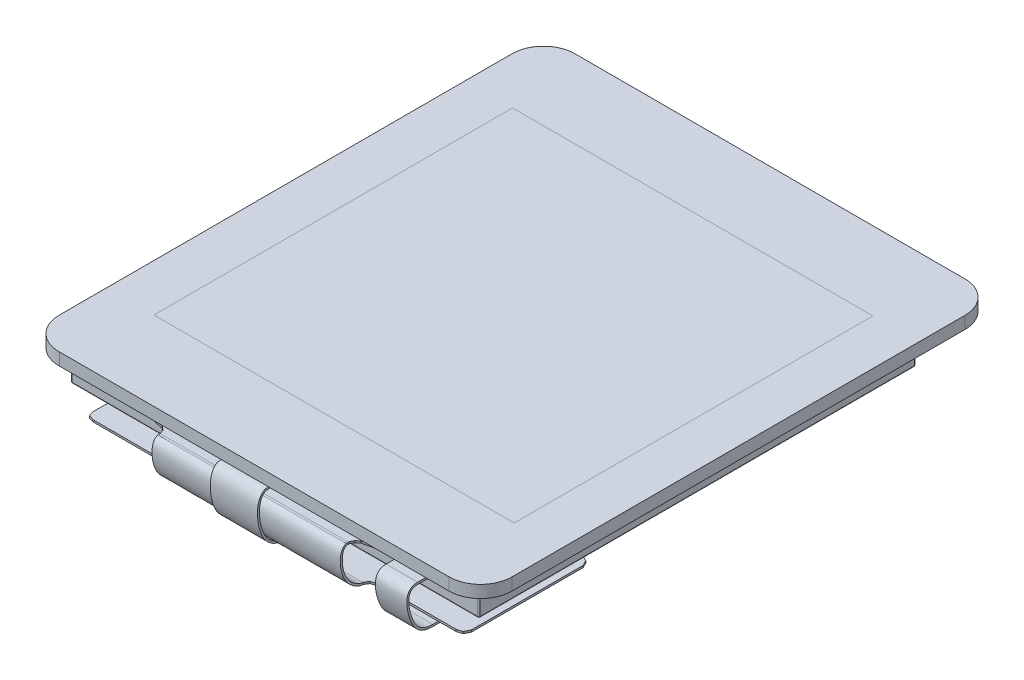
SolidWorks part; units mm, degrees
ref_plane "Ebene vorne" through (0, 0, 0) normal (0, 0, 1) x (1, 0, 0)
ref_plane "Ebene oben" through (0, 0, 0) normal (0, 1, 0) x (1, 0, 0)
ref_plane "Ebene rechts" through (0, 0, 0) normal (1, 0, 0) x (0, 0, -1)
sketch "Skizze1" plane through (0, 0, 0) normal (0, 1, 0) x (1, 0, 0)
  line L0 (-10.3006, -18.7379) -> (-10.4888, -18.361)
  line L1 (10.2585, -18.6958) -> (10.4, -18.361)
  line L4 (-14.0273, -22.8411) -> (-14.0273, -22.7993)
  line L5 (-14.0273, -22.7993) -> (-14.0691, -22.7993)
  line L6 (-14.0691, -22.7993) -> (-14.0691, -22.8411)
  line L7 (-14.0691, -22.8411) -> (-14.0273, -22.8411)
  line L8 (15.7018, -18.361) -> (15.7018, 15.346)
  line L9 (15.7018, 15.346) -> (-15.7858, 15.346)
  line L10 (-15.7858, 15.346) -> (-15.7858, -18.361)
  line L11 (-15.7858, -18.361) -> (15.7018, -18.361)
  line L12 (12.5614, -22.7993) -> (12.5614, -18.361)
  line L13 (10.1331, -22.7993) -> (10.1331, -18.361)
  line L14 (10.1331, -26.3167) -> (10.1331, -18.361)
  line L15 (12.5614, -26.3167) -> (12.5614, -18.361)
  line L16 (10.7611, -26.3167) -> (10.1331, -26.3167)
  line L17 (11.724, -26.3167) -> (10.9705, -26.3167)
  line L18 (11.5986, -26.0233) -> (11.5146, -26.3167)
  line L19 (11.1799, -26.3167) -> (11.0959, -26.0234)
  line L20 (10.9705, -26.3167) -> (10.9705, -26.2327)
  line L21 (10.9705, -26.2327) -> (10.8448, -26.1909)
  line L22 (10.8448, -26.1909) -> (10.7612, -26.2327)
  line L23 (10.7612, -26.2327) -> (10.7612, -26.3167)
  line L24 (10.6354, -26.0233) -> (10.4678, -26.3167)
  line L25 (12.2267, -26.3167) -> (12.1009, -26.0234)
  line L26 (12.0173, -26.3167) -> (11.9334, -26.2327)
  line L27 (11.9334, -26.2327) -> (11.8916, -26.1909)
  line L28 (11.8916, -26.1909) -> (11.724, -26.2327)
  line L29 (11.724, -26.2327) -> (11.724, -26.3167)
  line L30 (12.5614, -26.3167) -> (12.0173, -26.3167)
  line L31 (11.5986, -25.0187) -> (11.5986, -24.0137)
  line L32 (11.5986, -24.0137) -> (12.1009, -24.0137)
  line L33 (12.1009, -24.0137) -> (12.1009, -25.0187)
  line L34 (11.5986, -25.0187) -> (11.5146, -25.2699)
  line L35 (11.5146, -25.2699) -> (11.5986, -25.4792)
  line L36 (11.8915, -25.1441) -> (11.724, -25.1859)
  line L37 (11.724, -25.1859) -> (11.724, -25.3535)
  line L38 (11.724, -25.3535) -> (11.8915, -25.3953)
  line L39 (11.8915, -25.3953) -> (11.9334, -25.3535)
  line L40 (11.9334, -25.3535) -> (12.0173, -25.2699)
  line L41 (12.0173, -25.2699) -> (11.9334, -25.1859)
  line L42 (11.9334, -25.1859) -> (11.8915, -25.1441)
  line L43 (12.1009, -25.4792) -> (12.2267, -25.2699)
  line L44 (12.2267, -25.2699) -> (12.1009, -25.0187)
  line L45 (10.6354, -25.3535) -> (10.6354, -24.0137)
  line L46 (11.0959, -24.0137) -> (11.0959, -25.3535)
  line L47 (11.0959, -25.814) -> (11.0959, -26.0234)
  line L48 (10.6354, -25.814) -> (10.6354, -26.0234)
  line L49 (10.6354, -25.3535) -> (10.4678, -25.5628)
  line L50 (10.4678, -25.5628) -> (10.6354, -25.814)
  line L51 (10.8447, -25.3953) -> (10.7612, -25.4792)
  line L52 (10.7612, -25.4792) -> (10.7612, -25.6046)
  line L53 (10.7612, -25.6046) -> (10.8447, -25.6886)
  line L54 (10.8447, -25.6886) -> (10.9705, -25.6046)
  line L55 (10.9705, -25.6046) -> (10.9705, -25.4792)
  line L56 (10.9705, -25.4792) -> (10.8447, -25.3953)
  line L57 (11.0959, -25.814) -> (11.1799, -25.5628)
  line L58 (11.1799, -25.5628) -> (11.0959, -25.3535)
  line L59 (12.1009, -26.0233) -> (12.1009, -25.4792)
  line L60 (11.5986, -25.4792) -> (11.5986, -26.0233)
  line L61 (10.6354, -24.0137) -> (11.0959, -24.0137)
  line L62 (-13.9015, -13.8387) -> (-13.9015, 13.8387)
  line L63 (-13.9015, 13.8387) -> (13.9015, 13.8387)
  line L64 (13.9015, 13.8387) -> (13.9015, -13.8387)
  line L65 (13.9015, -13.8387) -> (-13.9015, -13.8387)
  line L77 (-7.3278, -19.8683) -> (-7.3278, -22.3806)
  line L78 (-10.1749, -18.8215) -> (-7.7465, -19.366)
  line L80 (-10.3006, -18.7379) -> (-10.1749, -18.8215)
  line L81 (-7.3278, -19.8683) -> (-7.4532, -19.5754)
  line L82 (-7.4532, -19.5754) -> (-7.7465, -19.366)
  line L83 (-7.3278, -19.8683) -> (-7.3278, -22.3806)
  line L84 (-7.7883, -22.8411) -> (-7.4532, -22.7158)
  line L85 (-7.4532, -22.7158) -> (-7.3278, -22.3806)
  line L86 (10.0491, -18.8215) -> (7.6207, -19.366)
  line L87 (10.0491, -18.8215) -> (10.2167, -18.7379)
  line L88 (10.2167, -18.7379) -> (10.2585, -18.6958)
  line L89 (7.6207, -19.366) -> (7.3696, -19.5754)
  line L90 (7.3696, -19.5754) -> (7.202, -19.8683)
  line L91 (7.202, -19.8683) -> (7.202, -22.3806)
  line L92 (3.5171, -58.2648) -> (-3.5593, -58.2648)
  line L93 (3.7265, -52.8214) -> (-3.7686, -52.8214)
  line L94 (3.5171, -58.2648) -> (3.6847, -58.223)
  line L95 (3.6847, -58.223) -> (3.7265, -58.0554)
  line L96 (3.7265, -53.2823) -> (3.7265, -33.8118)
  line L97 (-3.7687, -58.0554) -> (-3.6994, -58.223)
  line L98 (-3.6994, -58.223) -> (-3.5593, -58.2648)
  line L99 (-3.7687, -52.8214) -> (3.7265, -52.8214)
  line L100 (3.7265, -53.2823) -> (3.7265, -58.0554)
  line L101 (3.5171, -58.2648) -> (3.6847, -58.223)
  line L102 (3.6847, -58.223) -> (3.7265, -58.0554)
  line L103 (3.5171, -58.2648) -> (-3.5593, -58.2648)
  line L104 (-3.7687, -58.0554) -> (-3.6994, -58.223)
  line L105 (-3.6994, -58.223) -> (-3.5593, -58.2648)
  line L107 (-3.7687, -58.0554) -> (-3.7687, -33.8118)
  line L108 (-3.7687, -33.8118) -> (-4.1034, -32.9744)
  line L109 (-4.1034, -32.9744) -> (-5.0248, -32.6393)
  line L114 (13.9433, -22.8411) -> (7.7883, -22.8411)
  line L115 (-7.7883, -22.8411) -> (-14.0691, -22.8411)
  line L116 (-14.0691, -22.8411) -> (-14.4878, -22.9669)
  line L117 (-14.4878, -22.9669) -> (-14.6132, -23.3856)
  line L118 (7.202, -22.3806) -> (7.4114, -22.7158)
  line L119 (7.4114, -22.7158) -> (7.7883, -22.8412)
  line L120 (14.5714, -23.3856) -> (14.5714, -32.0112)
  line L121 (14.5714, -23.3856) -> (14.3621, -22.9669)
  line L122 (14.3621, -22.9669) -> (13.9434, -22.8412)
  line L123 (13.9433, -32.6393) -> (4.9409, -32.6393)
  line L124 (4.9409, -32.6393) -> (4.1034, -32.9744)
  line L125 (4.1034, -32.9744) -> (3.7265, -33.8118)
  line L126 (13.9433, -32.6393) -> (14.3621, -32.4299)
  line L127 (14.3621, -32.4299) -> (14.5714, -32.0112)
  line L128 (-5.0248, -32.6393) -> (-14.0691, -32.6393)
  line L129 (-14.6132, -23.3856) -> (-14.6132, -32.0112)
  line L130 (-14.6132, -32.0112) -> (-14.4878, -32.4299)
  line L131 (-14.4878, -32.4299) -> (-14.0691, -32.6393)
  line L132 (-3.0566, -25.3535) -> (-2.7219, -25.1859)
  line L133 (-2.7219, -25.1859) -> (-2.5961, -24.8512)
  line L134 (-2.5961, -24.8511) -> (-2.5961, -19.9519)
  line L135 (1.0466, -24.8511) -> (1.256, -25.1859)
  line L136 (1.256, -25.1859) -> (1.5911, -25.3535)
  line L137 (1.0466, -24.8511) -> (1.0466, -19.9519)
  line L138 (-8.5, -31.2995) -> (-11.3474, -31.2995)
  line L139 (-11.4728, -31.0901) -> (-11.4728, -31.2574)
  line L140 (-11.4728, -31.2574) -> (-11.3474, -31.2995)
  line L141 (-11.4728, -31.0901) -> (-11.4728, -27.9916)
  line L142 (-11.3474, -27.7822) -> (-11.4728, -27.824)
  line L143 (-11.4728, -27.824) -> (-11.4728, -27.9916)
  line L144 (-11.3474, -27.7822) -> (-8.5, -27.7822)
  line L145 (-8.5, -27.7822) -> (-8.5, -31.2995)
  line L146 (-11.4728, -31.0901) -> (-11.4728, -31.2574)
  line L147 (-11.4728, -31.2574) -> (-11.3474, -31.2995)
  line L148 (-11.4728, -31.0901) -> (-11.4728, -27.9916)
  line L149 (-11.3474, -27.7822) -> (-11.4728, -27.824)
  line L150 (-11.4728, -27.824) -> (-11.4728, -27.9916)
  line L151 (-11.3474, -27.7822) -> (-5.0248, -27.7822)
  line L152 (-5.0248, -27.7822) -> (-4.6897, -27.6146)
  line L153 (-4.6897, -27.6146) -> (-4.5221, -27.2795)
  line L154 (-14.0273, -22.8411) -> (-14.0273, -22.7993)
  line L155 (-14.0273, -22.7993) -> (-14.0691, -22.7993)
  line L156 (-14.0691, -22.7993) -> (-14.0691, -22.8411)
  line L157 (-14.0691, -22.8411) -> (-14.0273, -22.8411)
  line L158 (10.6354, -27.3635) -> (10.6354, -23.8044)
  line L159 (10.6354, -23.8044) -> (11.0959, -23.8044)
  line L160 (11.0959, -23.8044) -> (11.0959, -27.3635)
  line L161 (11.0959, -27.3635) -> (10.6354, -27.3635)
  line L162 (11.5986, -27.3635) -> (11.5986, -23.8044)
  line L163 (11.5986, -23.8044) -> (12.1009, -23.8044)
  line L164 (12.1009, -23.8044) -> (12.1009, -27.3635)
  line L165 (12.1009, -27.3635) -> (11.5986, -27.3635)
  line L166 (10.7611, -28.8708) -> (10.7611, -28.0334)
  line L167 (11.1799, -28.4521) -> (10.3424, -28.4521)
  line L168 (11.6822, -28.4521) -> (12.4778, -28.4521)
  line L169 (-7.7883, -24.1813) -> (-7.7883, -23.8044)
  line L170 (-7.7883, -23.8044) -> (-5.9877, -23.8044)
  line L171 (-5.9877, -23.8044) -> (-5.9877, -24.1813)
  line L172 (-5.9877, -24.1813) -> (-7.7883, -24.1813)
  line L173 (-7.7883, -24.8511) -> (-7.7883, -24.516)
  line L174 (-7.7883, -24.516) -> (-5.9877, -24.516)
  line L175 (-5.9877, -24.516) -> (-5.9877, -24.8511)
  line L176 (-5.9877, -24.8511) -> (-7.7883, -24.8511)
  line L177 (-7.7883, -25.4792) -> (-7.7883, -25.1441)
  line L178 (-7.7883, -25.1441) -> (-5.9877, -25.1441)
  line L179 (-5.9877, -25.1441) -> (-5.9877, -25.4792)
  line L180 (-5.9877, -25.4792) -> (-7.7883, -25.4792)
  line L181 (-7.7883, -26.1073) -> (-7.7883, -25.7722)
  line L182 (-7.7883, -25.7722) -> (-5.9877, -25.7722)
  line L183 (-5.9877, -25.7722) -> (-5.9877, -26.1073)
  line L184 (-5.9877, -26.1073) -> (-7.7883, -26.1073)
  line L185 (-11.8079, -24.1813) -> (-11.8079, -23.8044)
  line L186 (-11.8079, -23.8044) -> (-13.6504, -23.8044)
  line L187 (-13.6504, -23.8044) -> (-13.6504, -24.1813)
  line L188 (-13.6504, -24.1813) -> (-11.8079, -24.1813)
  line L189 (-11.8079, -24.8511) -> (-11.8079, -24.516)
  line L190 (-11.8079, -24.516) -> (-13.6504, -24.516)
  line L191 (-13.6504, -24.516) -> (-13.6504, -24.8511)
  line L192 (-13.6504, -24.8511) -> (-11.8079, -24.8511)
  line L193 (-11.8079, -25.4792) -> (-11.8079, -25.1441)
  line L194 (-11.8079, -25.1441) -> (-13.6504, -25.1441)
  line L195 (-13.6504, -25.1441) -> (-13.6504, -25.4792)
  line L196 (-13.6504, -25.4792) -> (-11.8079, -25.4792)
  line L197 (-11.8079, -26.1073) -> (-11.8079, -25.7722)
  line L198 (-11.8079, -25.7722) -> (-13.6504, -25.7722)
  line L199 (-13.6504, -25.7722) -> (-13.6504, -26.1073)
  line L200 (-13.6504, -26.1073) -> (-11.8079, -26.1073)
  line L201 (-11.3474, -31.2995) -> (-5.0248, -31.2995)
  line L202 (-4.5221, -31.8018) -> (-4.6897, -31.4667)
  line L203 (-4.6897, -31.4667) -> (-5.0248, -31.2995)
  line L204 (1.8005, -31.8018) -> (1.9262, -31.8018)
  line L205 (1.9262, -31.8018) -> (2.0098, -31.6343)
  line L206 (2.0098, -31.6343) -> (2.0098, -25.5628)
  line L207 (2.0098, -25.5628) -> (1.9262, -25.3953)
  line L208 (1.9262, -25.3953) -> (1.8005, -25.3535)
  line L209 (1.8005, -25.3535) -> (-4.3128, -25.3535)
  line L210 (-4.3128, -25.3535) -> (-4.4803, -25.3953)
  line L211 (-4.4803, -25.3953) -> (-4.5221, -25.5628)
  line L212 (-4.5221, -25.5628) -> (-4.5221, -31.6343)
  line L213 (-4.5221, -31.6343) -> (-4.4803, -31.8018)
  line L214 (-4.4803, -31.8018) -> (-4.3128, -31.8018)
  line L215 (-4.3128, -31.8018) -> (1.8005, -31.8018)
  line L216 (14.9901, -19.9519) -> (16.2463, -19.6589)
  line L217 (16.2463, -19.6589) -> (17.1674, -18.7379)
  line L218 (17.1674, -18.7379) -> (17.4189, -17.5235)
  line L219 (17.4189, -17.5235) -> (17.4189, 17.4396)
  line L220 (17.4189, 17.4396) -> (17.1674, 18.6957)
  line L221 (17.1674, 18.6957) -> (16.2463, 19.575)
  line L222 (16.2463, 19.575) -> (14.9902, 19.8683)
  line L223 (14.9901, 19.8683) -> (-15.0741, 19.8683)
  line L224 (-15.0741, 19.8683) -> (-16.2881, 19.575)
  line L225 (-16.2881, 19.575) -> (-17.1677, 18.6957)
  line L226 (-17.1677, 18.6957) -> (-17.5442, 17.4396)
  line L227 (-17.5443, 17.4396) -> (-17.5443, -17.5236)
  line L228 (-17.5443, -17.5235) -> (-17.1677, -18.7379)
  line L229 (-17.1677, -18.7379) -> (-16.2881, -19.6589)
  line L230 (-16.2881, -19.6589) -> (-15.0741, -19.9519)
  line L231 (-15.0741, -19.9519) -> (14.9902, -19.9519)
  line L232 (-13.9015, 13.8387) -> (-13.9015, -13.8387)
  line L233 (-13.9015, -13.8387) -> (13.9015, -13.8387)
  line L234 (13.9015, -13.8387) -> (13.9015, 13.8387)
  line L235 (13.9015, 13.8387) -> (-13.9015, 13.8387)
  line L236 (-12.5659, -28.1971) -> (-12.5659, -28.5322)
  line L237 (-12.5659, -28.5322) -> (-13.3197, -28.5322)
  line L238 (-13.3197, -28.5322) -> (-13.3197, -28.1971)
  line L239 (-13.3197, -28.1971) -> (-12.5659, -28.1971)
  line L240 (-12.5659, -28.6998) -> (-12.5659, -29.0349)
  line L241 (-12.5659, -29.0349) -> (-13.3197, -29.0349)
  line L242 (-13.3197, -29.0349) -> (-13.3197, -28.6998)
  line L243 (-13.3197, -28.6998) -> (-12.5659, -28.6998)
  line L244 (-12.5659, -29.2439) -> (-12.5659, -29.4951)
  line L245 (-12.5659, -29.4951) -> (-13.3197, -29.4951)
  line L246 (-13.3197, -29.4951) -> (-13.3197, -29.2439)
  line L247 (-13.3197, -29.2439) -> (-12.5659, -29.2439)
  line L248 (-12.5659, -29.7048) -> (-12.5659, -29.9977)
  line L249 (-12.5659, -29.9977) -> (-13.3197, -29.9977)
  line L250 (-13.3197, -29.9977) -> (-13.3197, -29.7048)
  line L251 (-13.3197, -29.7048) -> (-12.5659, -29.7048)
  line L252 (-12.5659, -30.2071) -> (-12.5659, -30.5001)
  line L253 (-12.5659, -30.5001) -> (-13.3197, -30.5001)
  line L254 (-13.3197, -30.5001) -> (-13.3197, -30.2071)
  line L255 (-13.3197, -30.2071) -> (-12.5659, -30.2071)
  line L256 (-12.5659, -30.7094) -> (-12.5659, -31.0446)
  line L257 (-12.5659, -31.0446) -> (-13.3197, -31.0446)
  line L258 (-13.3197, -31.0446) -> (-13.3197, -30.7094)
  line L259 (-13.3197, -30.7094) -> (-12.5659, -30.7094)
  point P1 (0, 0)
sketch "Skizze3" plane through (0, 0, 0) normal (0, 1, 0) x (1, 0, 0)
  line L0 (15.7018, -18.361) -> (15.7018, 15.346)
  line L1 (-15.7858, 15.346) -> (15.7018, 15.346)
  line L2 (-15.7858, 15.346) -> (-15.7858, -18.361)
  line L3 (-15.7858, -18.361) -> (15.7018, -18.361)
  point P0 (0, 0)
extrude "Aufsatz-Linear austragen1" add sketch "Skizze3" along normal blind 2.275
sketch "Skizze2" plane through (0, 0, 0) normal (0, 1, 0) x (1, 0, 0)
  line L3 (17.4189, -17.5232) -> (17.4189, 17.4396)
  line L7 (14.9901, 19.8683) -> (-15.0741, 19.8683)
  line L11 (-17.5443, 17.4396) -> (-17.5443, -17.5236)
  line L15 (-15.0741, -19.9519) -> (14.9902, -19.9519)
  arc A0 (-17.5443, 17.4396) -> (-15.0741, 19.8683) centre (-15.1152, 17.4396) cw
  arc A1 (14.9901, 19.8683) -> (17.4189, 17.4396) centre (14.9901, 17.4396) cw
  arc A2 (-17.5443, -17.5236) -> (-15.0741, -19.9519) centre (-15.1156, -17.5236) ccw
  arc A3 (14.9902, -19.9519) -> (17.4189, -17.5232) centre (14.9902, -17.5232) ccw
  point P0 (0, 0)
extrude "Aufsatz-Linear austragen2" add sketch "Skizze2" along normal offset from surface (0.95 mm away) 3.225 from surface separate body up to face at (-0.042, 0, 1.5075) starting at face at (-0.042, 2.275, 1.5075)
sketch "Skizze4" plane through (0, 3.225, 0) normal (0, 1, 0) x (1, 0, 0)
  line L0 (-13.9015, -13.8387) -> (-13.9015, 13.8387)
  line L1 (-13.9015, 13.8387) -> (13.9015, 13.8387)
  line L2 (13.9015, 13.8387) -> (13.9015, -13.8387)
  line L3 (13.9015, -13.8387) -> (-13.9015, -13.8387)
  point P0 (0, 0)
split line "Trennlinie1"
sketch "Skizze5" plane through (0, 0, 0) normal (0, 1, 0) x (1, 0, 0)
  line L0 (-10.3006, -18.7379) -> (-10.4888, -18.361)
  line L1 (-7.3278, -19.9519) -> (7.202, -19.9519)
  line L7 (-7.3278, -19.8683) -> (-7.4532, -19.5754)
  line L9 (10.0491, -18.8215) -> (7.6207, -19.366)
  line L10 (7.202, -19.9519) -> (7.202, -19.8683)
  line L11 (-15.0741, -19.9519) -> (14.9902, -19.9519) construction
  line L12 (7.3696, -19.5754) -> (7.6207, -19.366)
  line L13 (7.3696, -19.5754) -> (7.202, -19.8683)
  line L14 (10.0491, -18.8215) -> (10.1331, -18.7796)
  line L15 (-10.3006, -18.7379) -> (-10.1749, -18.8215)
  line L16 (-7.7465, -19.366) -> (-7.4532, -19.5754)
  line L17 (-10.4888, -18.361) -> (12.5614, -18.361)
  line L18 (10.1331, -19.9519) -> (12.5614, -19.9519)
  line L19 (-7.3278, -19.8683) -> (-7.3278, -19.9519)
  line L20 (10.1331, -18.7796) -> (10.1331, -19.9519)
  line L21 (12.5614, -18.361) -> (12.5614, -19.9519)
  line L22 (-10.1749, -18.8215) -> (-7.7465, -19.366)
  point P1 (0, 0)
extrude "Aufsatz-Linear austragen3" add sketch "Skizze5" along normal blind 0.15 from offset 1.5 separate body contours L15 L22 L16 L7 L19 L1 L10 L13 L12 L9 L14 L20 L18 L21 L17 L0 region at (1.315, 0, 19.1017)
sketch "Skizze6" plane through (0, 0, 0) normal (0, 1, 0) x (1, 0, 0)
  line L2 (-2.5961, -19.9519) -> (-2.5961, -18.361)
  line L3 (-15.7858, -18.361) -> (15.7018, -18.361) construction
  line L4 (-2.5961, -19.9519) -> (1.0466, -19.9519)
  line L5 (-2.5961, -18.361) -> (1.0466, -18.361)
  line L6 (-10.4888, -18.361) -> (12.5614, -18.361) construction
  line L7 (1.0466, -18.361) -> (1.0466, -19.9519)
  point P0 (0, 0)
extrude "Aufsatz-Linear austragen4" add sketch "Skizze6" against normal blind 0.15 from surface separate body starting at face at (-0.042, 2.275, 1.5075)
sketch "Skizze7" plane through (0, 0, 0) normal (0, 1, 0) x (1, 0, 0)
  line L194 (-13.3197, -10.4927) -> (-12.5659, -10.4927)
  line L195 (-13.3197, -10.1576) -> (-13.3197, -10.4927)
  line L196 (-12.5659, -10.1576) -> (-13.3197, -10.1576)
  line L197 (-12.5659, -10.4927) -> (-12.5659, -10.1576)
  line L198 (-13.3197, -10.995) -> (-12.5659, -10.995)
  line L199 (-13.3197, -10.7021) -> (-13.3197, -10.995)
  line L200 (-12.5659, -10.7021) -> (-13.3197, -10.7021)
  line L201 (-12.5659, -10.995) -> (-12.5659, -10.7021)
  line L202 (-13.3197, -11.4974) -> (-12.5659, -11.4974)
  line L203 (-13.3197, -11.2044) -> (-13.3197, -11.4974)
  line L204 (-12.5659, -11.2044) -> (-13.3197, -11.2044)
  line L205 (-12.5659, -11.4974) -> (-12.5659, -11.2044)
  line L206 (-13.3197, -11.9582) -> (-12.5659, -11.9582)
  line L207 (-13.3197, -11.7071) -> (-13.3197, -11.9582)
  line L208 (-12.5659, -11.7071) -> (-13.3197, -11.7071)
  line L209 (-12.5659, -11.9582) -> (-12.5659, -11.7071)
  line L210 (-13.3197, -12.5023) -> (-12.5659, -12.5023)
  line L211 (-13.3197, -12.1672) -> (-13.3197, -12.5023)
  line L212 (-12.5659, -12.1672) -> (-13.3197, -12.1672)
  line L213 (-12.5659, -12.5023) -> (-12.5659, -12.1672)
  line L214 (-13.3197, -13.005) -> (-12.5659, -13.005)
  line L215 (-13.3197, -12.6699) -> (-13.3197, -13.005)
  line L216 (-12.5659, -12.6699) -> (-13.3197, -12.6699)
  line L217 (-12.5659, -13.005) -> (-12.5659, -12.6699)
  line L218 (-9.5538, -5.8259) -> (-3.4405, -5.8259)
  line L219 (-9.7213, -5.8259) -> (-9.5537, -5.8259)
  line L220 (-9.7631, -5.9934) -> (-9.7213, -5.8259)
  line L221 (-9.7631, -12.0649) -> (-9.7631, -5.9934)
  line L222 (-9.7213, -12.2324) -> (-9.7631, -12.0649)
  line L223 (-9.5538, -12.2742) -> (-9.7213, -12.2324)
  line L224 (-3.4405, -12.2742) -> (-9.5537, -12.2742)
  line L225 (-3.3147, -12.2324) -> (-3.4405, -12.2742)
  line L226 (-3.2311, -12.0649) -> (-3.3147, -12.2324)
  line L227 (-3.2311, -5.9934) -> (-3.2311, -12.0649)
  line L228 (-3.3147, -5.8259) -> (-3.2311, -5.9934)
  line L229 (-3.4405, -5.8259) -> (-3.3147, -5.8259)
  line L230 (-9.9307, -6.161) -> (-10.2658, -6.3282)
  line L231 (-9.7631, -5.8259) -> (-9.9307, -6.161)
  line L232 (-11.3474, -9.9026) -> (-5.0248, -9.9026)
  line L233 (-13.6504, -15.0948) -> (-11.8079, -15.0948)
  line L234 (-13.6504, -15.43) -> (-13.6504, -15.0948)
  line L235 (-11.8079, -15.43) -> (-13.6504, -15.43)
  line L236 (-11.8079, -15.0948) -> (-11.8079, -15.43)
  line L237 (-13.6504, -15.7229) -> (-11.8079, -15.7229)
  line L238 (-13.6504, -16.058) -> (-13.6504, -15.7229)
  line L239 (-11.8079, -16.058) -> (-13.6504, -16.058)
  line L240 (-11.8079, -15.7229) -> (-11.8079, -16.058)
  line L241 (-13.6504, -16.351) -> (-11.8079, -16.351)
  line L242 (-13.6504, -16.6861) -> (-13.6504, -16.351)
  line L243 (-11.8079, -16.6861) -> (-13.6504, -16.6861)
  line L244 (-11.8079, -16.351) -> (-11.8079, -16.6861)
  line L245 (-13.6504, -17.0209) -> (-11.8079, -17.0209)
  line L246 (-13.6504, -17.3978) -> (-13.6504, -17.0209)
  line L247 (-11.8079, -17.3978) -> (-13.6504, -17.3978)
  line L248 (-11.8079, -17.0209) -> (-11.8079, -17.3978)
  line L249 (-5.9877, -15.0948) -> (-7.7883, -15.0948)
  line L250 (-5.9877, -15.43) -> (-5.9877, -15.0948)
  line L251 (-7.7883, -15.43) -> (-5.9877, -15.43)
  line L252 (-7.7883, -15.0948) -> (-7.7883, -15.43)
  line L253 (-5.9877, -15.7229) -> (-7.7883, -15.7229)
  line L254 (-5.9877, -16.058) -> (-5.9877, -15.7229)
  line L255 (-7.7883, -16.058) -> (-5.9877, -16.058)
  line L256 (-7.7883, -15.7229) -> (-7.7883, -16.058)
  line L257 (-5.9877, -16.351) -> (-7.7883, -16.351)
  line L258 (-5.9877, -16.6861) -> (-5.9877, -16.351)
  line L259 (-7.7883, -16.6861) -> (-5.9877, -16.6861)
  line L260 (-7.7883, -16.351) -> (-7.7883, -16.6861)
  line L261 (-5.9877, -17.0209) -> (-7.7883, -17.0209)
  line L262 (-5.9877, -17.3978) -> (-5.9877, -17.0209)
  line L263 (-7.7883, -17.3978) -> (-5.9877, -17.3978)
  line L264 (-7.7883, -17.0209) -> (-7.7883, -17.3978)
  line L265 (11.6822, -12.7501) -> (12.4778, -12.7501)
  line L266 (11.1799, -12.7501) -> (10.3424, -12.7501)
  line L267 (10.7611, -12.3313) -> (10.7611, -13.1688)
  line L268 (12.1009, -13.8387) -> (11.5986, -13.8387)
  line L269 (12.1009, -17.3978) -> (12.1009, -13.8387)
  line L270 (11.5986, -17.3978) -> (12.1009, -17.3978)
  line L271 (11.5986, -13.8387) -> (11.5986, -17.3978)
  line L272 (11.0959, -13.8387) -> (10.6354, -13.8387)
  line L273 (11.0959, -17.3978) -> (11.0959, -13.8387)
  line L274 (10.6354, -17.3978) -> (11.0959, -17.3978)
  line L275 (10.6354, -13.8387) -> (10.6354, -17.3978)
  line L280 (-9.9306, -10.0131) -> (-9.7631, -10.3482)
  line L281 (-10.2658, -9.8455) -> (-9.9306, -10.0131)
  line L282 (-22.0679, -9.8455) -> (-10.2658, -9.8455)
  line L283 (-11.4728, -13.3782) -> (-11.4728, -13.2106)
  line L284 (-22.0679, -9.8455) -> (-11.4728, -13.3782)
  line L285 (-11.4728, -10.112) -> (-11.4728, -13.2106)
  line L286 (-11.4728, -9.9448) -> (-11.3474, -9.9026)
  line L287 (-11.4728, -10.112) -> (-11.4728, -9.9448)
  line L288 (-8.5, -13.42) -> (-8.5, -9.9026)
  line L289 (-22.0679, -9.8455) -> (-8.5, -13.42)
  line L290 (-11.4728, -13.3782) -> (-11.4728, -13.2106)
  line L291 (-22.0679, -9.8455) -> (-11.4728, -13.3782)
  line L292 (-11.4728, -10.112) -> (-11.4728, -13.2106)
  line L293 (-11.4728, -9.9448) -> (-11.3474, -9.9026)
  line L294 (-11.4728, -10.112) -> (-11.4728, -9.9448)
  line L295 (-8.5, -9.9026) -> (-11.3474, -9.9026)
  line L296 (-3.985, -12.4418) -> (-3.6499, -12.2742)
  line L297 (-4.1944, -12.7766) -> (-3.985, -12.4418)
  line L298 (-7.9628, -12.4418) -> (-7.8371, -12.7766)
  line L299 (-8.2976, -12.2742) -> (-7.9628, -12.4418)
  line L300 (-14.4878, -8.7722) -> (-14.0691, -8.5629)
  line L301 (-14.6132, -9.191) -> (-14.4878, -8.7722)
  line L302 (-14.6132, -17.8165) -> (-14.6132, -9.1909)
  line L303 (-5.0248, -8.5629) -> (-14.0691, -8.5629)
  line L304 (14.3621, -8.7722) -> (14.5714, -9.191)
  line L305 (13.9433, -8.5629) -> (14.3621, -8.7722)
  line L306 (4.1034, -8.2277) -> (3.7265, -7.3903)
  line L307 (4.9409, -8.5629) -> (4.1034, -8.2277)
  line L308 (13.9433, -8.5629) -> (4.9409, -8.5629)
  line L309 (14.3621, -18.2352) -> (13.9434, -18.361)
  line L310 (14.5714, -17.8165) -> (14.3621, -18.2352)
  line L311 (14.5714, -17.8165) -> (14.5714, -9.1909)
  line L312 (7.4114, -18.4864) -> (7.7883, -18.361)
  line L313 (7.202, -18.8215) -> (7.4114, -18.4864)
  line L314 (-14.4878, -18.2352) -> (-14.6132, -17.8165)
  line L315 (-14.0691, -18.361) -> (-14.4878, -18.2352)
  line L316 (-7.7883, -18.361) -> (-14.0691, -18.361)
  line L317 (13.9433, -18.361) -> (7.7883, -18.361)
  line L318 (-4.1034, -8.2277) -> (-5.0248, -8.5629)
  line L319 (-3.7687, -7.3903) -> (-4.1034, -8.2277)
  line L320 (-3.7687, 16.8533) -> (-3.7687, -7.3903)
  line L321 (-3.6994, 17.0208) -> (-3.5593, 17.0627)
  line L322 (-3.7687, 16.8533) -> (-3.6994, 17.0208)
  line L323 (3.5171, 17.0626) -> (-3.5593, 17.0626)
  line L324 (3.6847, 17.0208) -> (3.7265, 16.8533)
  line L325 (3.5171, 17.0626) -> (3.6847, 17.0208)
  line L326 (3.7265, 12.0802) -> (3.7265, 16.8533)
  line L327 (-3.7687, 11.6193) -> (3.7265, 11.6193)
  line L328 (-3.6994, 17.0208) -> (-3.5593, 17.0627)
  line L329 (-3.7687, 16.8533) -> (-3.6994, 17.0208)
  line L330 (3.7265, 12.0802) -> (3.7265, -7.3903)
  line L331 (3.6847, 17.0208) -> (3.7265, 16.8533)
  line L332 (3.5171, 17.0626) -> (3.6847, 17.0208)
  line L333 (3.7265, 11.6193) -> (-3.7686, 11.6193)
  line L334 (3.5171, 17.0626) -> (-3.5593, 17.0626)
  line L335 (-7.4532, -18.4864) -> (-7.3278, -18.8215)
  line L336 (-7.7883, -18.361) -> (-7.4532, -18.4864)
  line L337 (10.6354, -17.1884) -> (11.0959, -17.1884)
  line L338 (11.5986, -15.7229) -> (11.5986, -15.1788)
  line L339 (12.1009, -15.1788) -> (12.1009, -15.7229)
  line L340 (11.1799, -15.6393) -> (11.0959, -15.8487)
  line L341 (11.0959, -15.3882) -> (11.1799, -15.6393)
  line L342 (10.9705, -15.7229) -> (10.8447, -15.8069)
  line L343 (10.9705, -15.5975) -> (10.9705, -15.7229)
  line L344 (10.8447, -15.5136) -> (10.9705, -15.5975)
  line L345 (10.7612, -15.5975) -> (10.8447, -15.5136)
  line L346 (10.7612, -15.7229) -> (10.7612, -15.5975)
  line L347 (10.8447, -15.8069) -> (10.7612, -15.7229)
  line L348 (10.4678, -15.6393) -> (10.6354, -15.3881)
  line L349 (10.6354, -15.8487) -> (10.4678, -15.6393)
  line L350 (10.6354, -15.3882) -> (10.6354, -15.1788)
  line L351 (11.0959, -15.3882) -> (11.0959, -15.1788)
  line L352 (11.0959, -17.1884) -> (11.0959, -15.8487)
  line L353 (10.6354, -15.8487) -> (10.6354, -17.1884)
  line L354 (12.2267, -15.9323) -> (12.1009, -16.1834)
  line L355 (12.1009, -15.7229) -> (12.2267, -15.9323)
  line L356 (11.9334, -16.0162) -> (11.8915, -16.058)
  line L357 (12.0173, -15.9323) -> (11.9334, -16.0162)
  line L358 (11.9334, -15.8487) -> (12.0173, -15.9323)
  line L359 (11.8915, -15.8069) -> (11.9334, -15.8487)
  line L360 (11.724, -15.8487) -> (11.8915, -15.8069)
  line L361 (11.724, -16.0162) -> (11.724, -15.8487)
  line L362 (11.8915, -16.058) -> (11.724, -16.0162)
  line L363 (11.5146, -15.9323) -> (11.5986, -15.7229)
  line L364 (11.5986, -16.1834) -> (11.5146, -15.9323)
  line L365 (12.1009, -17.1884) -> (12.1009, -16.1834)
  line L366 (11.5986, -17.1884) -> (12.1009, -17.1884)
  line L367 (11.5986, -16.1834) -> (11.5986, -17.1884)
  line L368 (12.5614, -14.8855) -> (12.0173, -14.8855)
  line L369 (11.724, -14.9694) -> (11.724, -14.8855)
  line L370 (11.8916, -15.0112) -> (11.724, -14.9694)
  line L371 (11.9334, -14.9694) -> (11.8916, -15.0112)
  line L372 (12.0173, -14.8855) -> (11.9334, -14.9694)
  line L373 (12.2267, -14.8855) -> (12.1009, -15.1788)
  line L374 (10.6354, -15.1788) -> (10.4678, -14.8855)
  line L375 (10.7612, -14.9694) -> (10.7612, -14.8855)
  line L376 (10.8448, -15.0112) -> (10.7612, -14.9694)
  line L377 (10.9705, -14.9694) -> (10.8448, -15.0112)
  line L378 (10.9705, -14.8855) -> (10.9705, -14.9694)
  line L379 (11.1799, -14.8855) -> (11.0959, -15.1788)
  line L380 (11.5986, -15.1788) -> (11.5146, -14.8855)
  line L381 (11.724, -14.8855) -> (10.9705, -14.8855)
  line L382 (10.7611, -14.8855) -> (10.1331, -14.8855)
  point P0 (-5.241, -9.9504)
  point P1 (0, 0)
sketch "Skizze8" plane through (0, 0, 0) normal (0, 1, 0) x (1, 0, 0)
  line L24 (-7.3278, -18.8215) -> (7.202, -18.8215)
  line L25 (7.7883, -18.361) -> (13.9433, -18.361)
  line L26 (-3.7687, -7.3903) -> (-4.1034, -8.2277)
  line L27 (3.7265, -7.3903) -> (4.1034, -8.2277)
  line L28 (4.9409, -8.5629) -> (13.9433, -8.5629)
  line L29 (14.3621, -8.7722) -> (14.5714, -9.1909)
  line L30 (14.5714, -17.8165) -> (14.3621, -18.2352)
  line L31 (7.7883, -18.361) -> (7.4114, -18.4864)
  line L32 (-5.0248, -8.5629) -> (-14.0691, -8.5629)
  line L33 (-14.4878, -8.7722) -> (-14.6132, -9.1909)
  line L34 (-14.6132, -17.8165) -> (-14.4878, -18.2352)
  line L35 (-14.0691, -18.361) -> (-7.7883, -18.361)
  line L36 (-7.4532, -18.4864) -> (-7.3278, -18.8215)
  line L37 (4.1034, -8.2277) -> (4.9409, -8.5629)
  line L38 (13.9433, -8.5629) -> (14.3621, -8.7722)
  line L71 (14.5714, -9.1909) -> (14.5714, -17.8165)
  line L72 (14.3621, -18.2352) -> (13.9433, -18.361)
  line L73 (7.4114, -18.4864) -> (7.202, -18.8215)
  line L82 (-7.4532, -18.4864) -> (-7.7883, -18.361)
  line L83 (-14.0691, -18.361) -> (-14.4878, -18.2352)
  line L84 (-14.6132, -17.8165) -> (-14.6132, -9.1909)
  line L85 (-5.0248, -8.5629) -> (-4.1034, -8.2277)
  line L86 (-14.4878, -8.7722) -> (-14.0691, -8.5629)
  line L87 (-3.7687, -7.3903) -> (-3.7687, 16.8533)
  line L89 (3.7265, -7.3903) -> (3.7265, 16.8533)
  line L90 (-3.5593, 17.0627) -> (3.5171, 17.0627)
  line L91 (-3.7687, 16.8533) -> (-3.6994, 17.0208)
  line L92 (3.7265, 16.8533) -> (3.6847, 17.0209)
  line L93 (-3.6994, 17.0208) -> (-3.5593, 17.0627)
  line L94 (3.5171, 17.0627) -> (3.6847, 17.0209)
  line L96 (-3.7687, 8.4252) -> (3.7265, 8.4252)
  line L119 (13.9433, -18.361) -> (7.7883, -18.361)
  point P1 (0, 0)
extrude "Aufsatz-Linear austragen5" add sketch "Skizze8" against normal blind 0.15 from offset 1.6 separate body contours L94 L90 L93 L91 L87 L26 L85 L32 L86 L33 L84 L34 L83 L35 L82 L36 L24 L73 L31 L25 L72 L30 L71 L29 L38 L28 L37 L27 L89 L92 region at (-0.0231, 0, 9.4807) offset against normal yes
sketch "Skizze9" plane through (0, 0, 0) normal (0, 1, 0) x (1, 0, 0)
  line L0 (-2.5961, -18.7299) -> (1.0466, -18.7299)
  line L1 (-3.0566, -15.8487) -> (-4.3128, -15.8487)
  line L2 (-5.0248, -13.42) -> (-4.6897, -13.5875)
  line L3 (-4.5221, -13.9226) -> (-4.5221, -15.6393)
  line L4 (-4.4803, -15.8069) -> (-4.3128, -15.8487)
  line L5 (-3.0566, -15.8487) -> (-2.7219, -16.0162)
  line L6 (1.0466, -16.351) -> (1.256, -16.0162)
  line L7 (1.5911, -15.8487) -> (1.8005, -15.8487)
  line L9 (1.9262, -15.8069) -> (2.0098, -15.6393)
  line L10 (-11.3474, -9.9026) -> (-11.4728, -9.9448)
  line L11 (-11.3474, -13.42) -> (-11.4728, -13.3782)
  line L12 (-4.6897, -13.5875) -> (-4.5221, -13.9226)
  line L13 (-4.5221, -15.6393) -> (-4.4803, -15.8069)
  line L14 (-2.7219, -16.0162) -> (-2.5961, -16.351)
  line L16 (-5.0248, -9.9026) -> (-4.6897, -9.7354)
  line L17 (1.256, -16.0162) -> (1.5911, -15.8487)
  line L18 (2.0098, -15.6393) -> (2.0098, -9.5679)
  line L19 (-4.6897, -9.7354) -> (-4.5221, -9.4003)
  line L20 (-5.0248, -9.9026) -> (-11.3474, -9.9026)
  line L21 (-5.9362, -9.9026) -> (-5.9362, -13.42)
  line L38 (-4.5221, -9.4003) -> (1.9262, -9.4003)
  line L45 (1.9262, -15.8069) -> (1.8005, -15.8487)
  line L48 (1.9262, -9.4003) -> (2.0098, -9.5679)
  line L58 (-11.4728, -9.9448) -> (-11.4728, -13.3782)
  line L62 (-11.3474, -13.42) -> (-5.0248, -13.42)
  line L65 (-11.4728, -9.9448) -> (-11.4728, -13.3782)
  line L69 (1.0466, -16.351) -> (1.0466, -18.7299)
  line L72 (-2.5961, -16.351) -> (-2.5961, -18.7299)
  point P4 (0, 0)
extrude "Aufsatz-Linear austragen6" add sketch "Skizze9" against normal blind 0.15 from surface separate body contours L14 L72 L0 L69 L6 L17 L7 L45 L9 L18 L48 L38 L19 L16 L20 L10 L58 L11 L62 L2 L12 L3 L13 L4 L1 L5 region at (-1.5183, 0, 13.3935) starting at face at (-0.0355, -1.75, 11.7203)
sketch "Skizze10" plane through (0, 0, 0) normal (1, 0, 0) x (0, 0, -1)
  line L0 (-19.9519, 1.5) -> (-19.9519, 1.65)
  line L1 (-18.8215, -1.6) -> (-18.8215, -1.75)
  line L4 (-20.1019, 1.6299) -> (-20.1019, 1.65) construction
  line L5 (-18.9715, -1.7346) -> (-18.9715, -1.75) construction
  arc A0 (-20.1019, 1.6299) -> (-19.9519, 1.65) centre (-19.9567, 1.1166) cw
  arc A1 (-18.8215, -1.75) -> (-18.9715, -1.7346) centre (-18.8215, -1.0126) cw
  spline S0 degree 3 poles (-19.9519, 1.5) (-20.5381, 1.5) (-20.4456, 0.116) (-19.8473, -1.1972) (-19.1556, -1.6) (-18.8215, -1.6) knots 0 0 0 0 0.401622 0.501622 1 1 1 1
  spline S1 degree 1 poles (-20.1019, 1.6299) (-18.9715, -1.7346) knots 0 0 1 1 construction
  spline S2 degree 3 poles (-20.1019, 1.6299) (-20.1984, 1.6026) (-20.3769, 1.4788) (-20.5455, 1.1191) (-20.5815, 0.5548) (-20.4618, -0.1651) (-20.2543, -0.6952) (-19.971, -1.0991) (-19.6408, -1.4173) (-19.2913, -1.6365) (-19.0848, -1.7125) (-18.9715, -1.7346) knots 0.026925 0.026925 0.026925 0.026925 0.084237 0.14155 0.256175 0.3708 0.485424 0.600049 0.714674 0.829299 0.943924 0.943924 0.943924 0.943924
  dimension "D1" = 0.15
extrude "Aufsatz-Linear austragen7" add sketch "Skizze10" along normal up to vertex (7.202 mm away) and the other way up to vertex (7.3278 mm away) up to point (7.202, 1.5, 19.9519) other way up to point (-7.3278, -1.75, 18.8215)
sketch "Skizze11" plane through (0, 0, 0) normal (1, 0, 0) x (0, 0, -1)
  line L0 (-18.7299, -1.9) -> (-18.7299, -1.75)
  line L1 (-19.9519, 2.275) -> (-19.9519, 2.125)
  spline S0 degree 3 poles (-19.9519, 2.275) (-20.7319, 2.275) (-20.9442, 0.9749) (-20.3068, -1.5688) (-19.3098, -1.9) (-18.7299, -1.9) knots 0 0 0 0 0.380799 0.480799 1 1 1 1
  spline S1 degree 1 poles (-19.9519, 2.125) (-18.7299, -1.75) knots 0 0 1 1 construction
  spline S2 degree 3 poles (-19.9519, 2.125) (-20.0429, 2.125) (-20.2356, 2.0811) (-20.4795, 1.8553) (-20.7534, 1.041) (-20.4523, -0.7497) (-19.7491, -1.4807) (-19.1373, -1.7206) (-18.87, -1.75) (-18.7299, -1.75) knots 0 0 0 0 0.0625 0.125 0.25 0.5 0.75 0.875 1 1 1 1
  dimension "D1" = 0.15
extrude "Aufsatz-Linear austragen8" add sketch "Skizze11" against normal up to vertex (2.5961 mm away) and the other way up to vertex (1.0466 mm away) up to point (-2.5961, 2.275, 19.9519) other way up to point (1.0466, 2.275, 19.9519)
sketch "Skizze12" plane through (0, 0, 0) normal (0, 1, 0) x (1, 0, 0)
  line L0 (10.6354, -14.8855) -> (10.6354, -15.4029)
  line L1 (10.6354, -17.1884) -> (11.0959, -17.1884)
  line L2 (11.0959, -17.1884) -> (11.0959, -15.8757)
  line L3 (11.5986, -14.8855) -> (11.5986, -15.7247)
  line L10 (11.5986, -17.1884) -> (12.1009, -17.1884)
  line L11 (12.1009, -17.1884) -> (12.1009, -16.1527)
  line L12 (10.1331, -14.8855) -> (10.7557, -14.8855)
  line L13 (10.9757, -14.8855) -> (11.7397, -14.8855)
  line L14 (11.9597, -14.8855) -> (12.5614, -14.8855)
  line L15 (11.5986, -16.1527) -> (11.5986, -17.1884)
  line L24 (12.1009, -15.7247) -> (12.1009, -14.8855)
  line L25 (10.6354, -15.8757) -> (10.6354, -17.1884)
  line L26 (11.0959, -15.4029) -> (11.0959, -14.8855)
  line L40 (10.1331, -18.7796) -> (10.1331, -14.8855)
  line L41 (12.5614, -14.8855) -> (12.5614, -18.7796)
  line L42 (12.5614, -18.361) -> (12.5614, -19.9519) construction
  line L43 (12.5614, -18.7796) -> (10.1331, -18.7796)
  circle A0 centre (10.8657, -15.6393) radius 0.15
  circle A1 centre (11.8497, -15.9387) radius 0.15
  arc A2 (11.0959, -15.8757) -> (11.0959, -15.4029) centre (10.8657, -15.6393) ccw
  arc A3 (11.5986, -15.7247) -> (11.5986, -16.1527) centre (11.8497, -15.9387) ccw
  arc A4 (10.7557, -14.8855) -> (10.9757, -14.8855) centre (10.8657, -14.8855) ccw
  arc A5 (11.7397, -14.8855) -> (11.9597, -14.8855) centre (11.8497, -14.8855) ccw
  arc A6 (10.6354, -15.4029) -> (10.6354, -15.8757) centre (10.8657, -15.6393) ccw
  arc A7 (12.1009, -16.1527) -> (12.1009, -15.7247) centre (11.8497, -15.9387) ccw
  point P0 (0, 0)
extrude "Aufsatz-Linear austragen9" add sketch "Skizze12" against normal blind 0.15 from surface separate body contours A7 L11 L10 L15 A3 L3 L13 L26 A2 L2 L1 L25 A6 L0 L12 L40 L43 L41 L14 L24 | L11 A7 L24 L14 A5 L13 L3 A3 L15 L10 A1 | L0 A6 L25 L1 L2 A2 L26 L13 A4 L12 A0 region at (10.8657, 0, 16.0594) region at (11.3385, 0, 17.0967) region at (11.6692, 0, 14.9094) starting at face at (-0.134, -1.75, 12.661)
sketch "Skizze13" plane through (0, 0, 0) normal (1, 0, 0) x (0, 0, -1)
  line L0 (-19.9519, 1.65) -> (-19.9519, 1.5)
  line L2 (-18.7796, -1.9) -> (-18.7796, -1.75)
  spline S0 degree 3 poles (-19.9519, 1.65) (-21.0132, 1.65) (-20.7532, -0.6413) (-19.8315, -1.9) (-18.7796, -1.9) knots 0 0 0 0 0.524833 1 1 1 1
  spline S1 degree 3 poles (-19.9519, 2.275) (-20.7319, 2.275) (-20.9442, 0.9749) (-20.3068, -1.5688) (-19.3098, -1.9) (-18.7299, -1.9) knots 0 0 0 0 0.380799 0.480799 1 1 1 1 construction
  spline S2 degree 1 poles (-19.9519, 1.5) (-18.7796, -1.75) knots 0 0 1 1 construction
  spline S3 degree 3 poles (-19.9519, 1.5) (-20.0469, 1.5) (-20.2589, 1.4692) (-20.4279, 1.3625) (-20.5514, 1.2012) (-20.6483, 0.8978) (-20.6413, 0.3828) (-20.4703, -0.3059) (-20.2312, -0.9183) (-19.9137, -1.3771) (-19.5419, -1.6228) (-19.1541, -1.7304) (-18.8998, -1.75) (-18.7796, -1.75) knots 0 0 0 0 0.0625 0.125 0.1875 0.25 0.375 0.5 0.625 0.75 0.875 0.9375 1 1 1 1
  dimension "D1" = 0.15
extrude "Aufsatz-Linear austragen11" add sketch "Skizze13" along normal up to vertex (12.5614 mm away) from vertex up to point (12.5614, 1.65, 19.9519) starting at point (10.1331, 1.65, 19.9519)
sketch "Skizze14" plane through (0, -1.75, 0) normal (0, 1, 0) x (1, 0, 0)
  line L0 (-13.2862, -10.5672) -> (-12.5324, -10.5672)
  line L1 (-13.2862, -10.2321) -> (-13.2862, -10.5672)
  line L2 (-12.5324, -10.2321) -> (-13.2862, -10.2321)
  line L3 (-12.5324, -10.5672) -> (-12.5324, -10.2321)
  line L4 (-13.2862, -11.0695) -> (-12.5324, -11.0695)
  line L5 (-13.2862, -10.7474) -> (-13.2862, -11.0695)
  line L6 (-12.5324, -10.7474) -> (-13.2862, -10.7474)
  line L7 (-12.5324, -11.0695) -> (-12.5324, -10.7474)
  line L8 (-13.2862, -11.5718) -> (-12.5324, -11.5718)
  line L9 (-13.2862, -11.2545) -> (-13.2862, -11.5718)
  line L10 (-12.5324, -11.2545) -> (-13.2862, -11.2545)
  line L11 (-12.5324, -11.5718) -> (-12.5324, -11.2545)
  line L12 (-13.2862, -12.0843) -> (-12.5324, -12.0843)
  line L13 (-13.2862, -11.7532) -> (-13.2862, -12.0843)
  line L14 (-12.5324, -11.7532) -> (-13.2862, -11.7532)
  line L15 (-12.5324, -12.0843) -> (-12.5324, -11.7532)
  line L16 (-13.2862, -12.5768) -> (-12.5324, -12.5768)
  line L17 (-13.2862, -12.2417) -> (-13.2862, -12.5768)
  line L18 (-12.5324, -12.2417) -> (-13.2862, -12.2417)
  line L19 (-12.5324, -12.5768) -> (-12.5324, -12.2417)
  line L20 (-13.2862, -13.0795) -> (-12.5324, -13.0795)
  line L21 (-13.2862, -12.7444) -> (-13.2862, -13.0795)
  line L22 (-12.5324, -12.7444) -> (-13.2862, -12.7444)
  line L23 (-12.5324, -13.0795) -> (-12.5324, -12.7444)
  line L24 (-13.6504, -15.0948) -> (-11.8079, -15.0948)
  line L25 (-13.6504, -15.43) -> (-13.6504, -15.0948)
  line L26 (-11.8079, -15.43) -> (-13.6504, -15.43)
  line L27 (-11.8079, -15.0948) -> (-11.8079, -15.43)
  line L28 (-13.6504, -15.7229) -> (-11.8079, -15.7229)
  line L29 (-13.6504, -16.058) -> (-13.6504, -15.7229)
  line L30 (-11.8079, -16.058) -> (-13.6504, -16.058)
  line L31 (-11.8079, -15.7229) -> (-11.8079, -16.058)
  line L32 (-13.6504, -16.351) -> (-11.8079, -16.351)
  line L33 (-13.6504, -16.6861) -> (-13.6504, -16.351)
  line L34 (-11.8079, -16.6861) -> (-13.6504, -16.6861)
  line L35 (-11.8079, -16.351) -> (-11.8079, -16.6861)
  line L36 (-13.6504, -17.0209) -> (-11.8079, -17.0209)
  line L37 (-13.6504, -17.3978) -> (-13.6504, -17.0209)
  line L38 (-11.8079, -17.3978) -> (-13.6504, -17.3978)
  line L39 (-11.8079, -17.0209) -> (-11.8079, -17.3978)
  line L40 (-5.9877, -15.0948) -> (-7.7883, -15.0948)
  line L41 (-5.9877, -15.43) -> (-5.9877, -15.0948)
  line L42 (-7.7883, -15.43) -> (-5.9877, -15.43)
  line L43 (-7.7883, -15.0948) -> (-7.7883, -15.43)
  line L44 (-5.9877, -15.7229) -> (-7.7883, -15.7229)
  line L45 (-5.9877, -16.058) -> (-5.9877, -15.7229)
  line L46 (-7.7883, -16.058) -> (-5.9877, -16.058)
  line L47 (-7.7883, -15.7229) -> (-7.7883, -16.058)
  line L48 (-5.9877, -16.351) -> (-7.7883, -16.351)
  line L49 (-5.9877, -16.6861) -> (-5.9877, -16.351)
  line L50 (-7.7883, -16.6861) -> (-5.9877, -16.6861)
  line L51 (-7.7883, -16.351) -> (-7.7883, -16.6861)
  line L52 (-5.9877, -17.0209) -> (-7.7883, -17.0209)
  line L53 (-5.9877, -17.3978) -> (-5.9877, -17.0209)
  line L54 (-7.7883, -17.3978) -> (-5.9877, -17.3978)
  line L55 (-7.7883, -17.0209) -> (-7.7883, -17.3978)
  line L56 (12.1009, -13.8387) -> (11.5986, -13.8387)
  line L57 (12.1009, -17.3978) -> (12.1009, -13.8387)
  line L58 (11.5986, -17.3978) -> (12.1009, -17.3978)
  line L59 (11.5986, -13.8387) -> (11.5986, -17.3978)
  line L60 (11.0959, -13.8387) -> (10.6354, -13.8387)
  line L61 (11.0959, -17.3978) -> (11.0959, -13.8387)
  line L62 (10.6354, -17.3978) -> (11.0959, -17.3978)
  line L63 (10.6354, -13.8387) -> (10.6354, -17.3978)
  line L64 (11.0959, -17.1884) -> (11.0959, -15.8487)
  line L65 (10.6354, -15.8487) -> (10.6354, -17.1884)
  line L66 (12.1009, -17.1884) -> (12.1009, -16.1834)
  line L67 (11.5986, -16.1834) -> (11.5986, -17.1884)
  point P0 (0, 0)
split line "Trennlinie2"
sketch "Skizze16" plane through (0, -1.9, 0) normal (0, -1, 0) x (1, 0, 0)
  line L0 (10.7557, 14.8855) -> (10.6354, 14.8855)
  line L1 (11.9597, 14.8855) -> (12.1009, 14.8855)
  line L2 (11.5986, 14.8855) -> (11.7397, 14.8855)
  line L12 (11.0959, 15.4029) -> (11.0959, 14.8855)
  line L13 (10.6354, 15.8757) -> (10.6354, 17.1884)
  line L14 (12.1009, 15.7247) -> (12.1009, 14.8855)
  line L15 (11.5986, 16.1527) -> (11.5986, 17.1884)
  line L16 (10.9757, 14.8855) -> (11.0959, 14.8855)
  line L17 (12.1009, 17.1884) -> (12.1009, 16.1527)
  line L18 (11.5986, 17.1884) -> (12.1009, 17.1884)
  line L19 (11.5986, 14.8855) -> (11.5986, 15.7247)
  line L20 (11.0959, 17.1884) -> (11.0959, 15.8757)
  line L21 (10.6354, 17.1884) -> (11.0959, 17.1884)
  line L22 (10.6354, 14.8855) -> (10.6354, 15.4029)
  arc A8 (12.1009, 16.1527) -> (12.1009, 15.7247) centre (11.8497, 15.9387) cw
  arc A9 (10.6354, 15.4029) -> (10.6354, 15.8757) centre (10.8657, 15.6393) cw
  arc A10 (11.7397, 14.8855) -> (11.9597, 14.8855) centre (11.8497, 14.8855) cw
  arc A11 (10.7557, 14.8855) -> (10.9757, 14.8855) centre (10.8657, 14.8855) cw
  arc A12 (11.5986, 15.7247) -> (11.5986, 16.1527) centre (11.8497, 15.9387) cw
  arc A13 (11.0959, 15.8757) -> (11.0959, 15.4029) centre (10.8657, 15.6393) cw
  circle A14 centre (11.8497, 15.9387) radius 0.15
  circle A15 centre (10.8657, 15.6393) radius 0.15
  point P73 (0, 0)
split line "Trennlinie3"
sketch "Skizze17" plane through (0, 0, 14.8855) normal (0, 0, -1) x (-1, 0, 0)
  line L0 (-10.6354, -1.9) -> (-10.6354, -1.75)
  line L1 (-10.6354, -1.75) -> (-11.0959, -1.75)
  line L2 (-11.0959, -1.75) -> (-11.0959, -1.9)
  line L3 (-11.0959, -1.9) -> (-10.6354, -1.9)
  line L4 (-11.5986, -1.9) -> (-11.5986, -1.75)
  line L5 (-11.5986, -1.75) -> (-12.1009, -1.75)
  line L6 (-12.1009, -1.75) -> (-12.1009, -1.9)
  line L7 (-12.1009, -1.9) -> (-11.5986, -1.9)
split line "Trennlinie4"
fillet "Verrundung1" radius 0.1 8 edges at (-15.7858, 1.1375, 18.361) (-15.7858, 0, 1.5075) (-15.7858, 1.1375, -15.346) (-0.042, 0, -15.346) (15.7018, 1.1375, -15.346) (-0.042, 0, 18.361) (15.7018, 0, 1.5075) (15.7018, 1.1375, 18.361)
sketch "Skizze19" plane through (0, 0, 0) normal (0, 1, 0) x (1, 0, 0)
  line L0 (-3.5593, 17.0627) -> (3.5171, 17.0627)
  line L1 (-3.7687, 16.8533) -> (-3.6994, 17.0208)
  line L2 (3.7265, 16.8533) -> (3.6847, 17.0209)
  line L3 (-3.6994, 17.0208) -> (-3.5593, 17.0627)
  line L4 (3.5171, 17.0627) -> (3.6847, 17.0209)
  line L5 (-3.7687, 11.899) -> (3.7265, 11.899)
  line L6 (-3.7687, 16.8533) -> (-3.7687, 11.899)
  line L7 (3.7265, 16.8533) -> (3.7265, 11.899)
  point P1 (0, 0)
extrude "Aufsatz-Linear austragen12" add sketch "Skizze19" against normal blind 0.15 from offset 2.3 separate body offset against normal yes
sketch "Skizze20" plane through (-3.7687, 0, 0) normal (-1, 0, 0) x (0, 0, 1)
  line L0 (-11.899, -2.45) -> (-11.899, -2.3) construction
  line L1 (-8.4252, -1.75) -> (-8.4252, -1.6) construction
  line L2 (-11.899, -2.3) -> (-11.899, -2.45)
  line L3 (-8.4252, -1.6) -> (-8.4252, -1.75)
  spline S0 degree 3 poles (-11.899, -2.375) (-10.8936, -2.375) (-10.0606, -1.9627) (-9.3284, -1.675) (-8.4252, -1.675) knots 0 0 0 0 0.543124 1 1 1 1
  spline S1 degree 1 poles (-11.899, -2.45) (-8.4252, -1.75) knots 0 0 1 1 construction
  spline S2 degree 3 poles (-11.899, -2.45) (-11.789, -2.45) (-11.5594, -2.444) (-11.1771, -2.4111) (-10.7757, -2.3366) (-10.398, -2.2129) (-10.0841, -2.076) (-9.8028, -1.9483) (-9.4952, -1.8435) (-9.1418, -1.7819) (-8.776, -1.7549) (-8.5375, -1.75) (-8.4252, -1.75) knots 0 0 0 0 0.0625 0.125 0.25 0.375 0.5 0.625 0.75 0.875 0.9375 1 1 1 1
  spline S3 degree 1 poles (-11.899, -2.3) (-8.4252, -1.6) knots 0 0 1 1 construction
  spline S4 degree 3 poles (-11.899, -2.3) (-11.7917, -2.3) (-11.5674, -2.2941) (-11.1971, -2.2622) (-10.8122, -2.1906) (-10.4524, -2.0728) (-10.1474, -1.9401) (-9.8606, -1.8096) (-9.5309, -1.6971) (-9.1593, -1.6327) (-8.7824, -1.605) (-8.5398, -1.6) (-8.4252, -1.6) knots 0 0 0 0 0.0625 0.125 0.25 0.375 0.5 0.625 0.75 0.875 0.9375 1 1 1 1
  line M2 (-8.4252, -1.6) -> (-8.4252, -1.75)
  dimension "D1" = 0.075
  dimension "D2" = 0.075
extrude "Aufsatz-Linear austragen13" add sketch "Skizze20" against normal up to vertex (7.4952 mm away) contours S4 L2 S0 M2 | S2 L3 S4 L2 region at (-3.7687, -1.9841, -10.1624) up to point (3.7265, -1.75, -8.4252)
sketch "Skizze22" plane through (0, 0, 0) normal (0, 1, 0) x (1, 0, 0)
  line L0 (-3.5593, 17.0627) -> (3.5171, 17.0627)
  line L1 (-3.7687, 16.8533) -> (-3.6994, 17.0208)
  line L2 (3.7265, 16.8533) -> (3.6847, 17.0209)
  line L3 (-3.6994, 17.0208) -> (-3.5593, 17.0627)
  line L4 (3.5171, 17.0627) -> (3.6847, 17.0209)
  line L6 (-0.0211, 11.8964) -> (-3.7687, 11.8964)
  line L7 (-3.7687, 11.8964) -> (-3.7687, 16.8533)
  line L8 (-0.0211, 11.8964) -> (3.7265, 11.8964)
  line L9 (3.7265, 11.8964) -> (3.7265, 16.8533)
  point P0 (0, 0)
extrude "Aufsatz-Linear austragen14" add sketch "Skizze22" against normal blind 0.15 from surface separate body starting at face at (-0.0176, -2.45, -15.709)
sketch "Skizze24" plane through (0, 0, 0) normal (0, 1, 0) x (1, 0, 0)
  line L0 (-11.3474, -9.9026) -> (-11.4728, -9.9448)
  line L1 (-11.3474, -13.42) -> (-11.4728, -13.3782)
  line L2 (-8.5246, -9.9026) -> (-8.5246, -13.42)
  line L3 (-11.4728, -9.9448) -> (-11.4728, -13.3782)
  line L4 (-11.4728, -9.9448) -> (-11.4728, -13.3782)
  line L5 (-11.3474, -9.9026) -> (-8.5246, -9.9026)
  line L6 (-11.3474, -13.42) -> (-8.5246, -13.42)
  point P2 (0, 0)
extrude "Aufsatz-Linear austragen15" add sketch "Skizze24" against normal blind 0.15 from offset 2.1 separate body contours L1 L6 L2 L5 L0 L3 region at (-9.998, 0, 11.6613) offset against normal yes
sketch "Skizze25" plane through (0, 0, 9.9026) normal (0, 0, -1) x (-1, 0, 0)
  line L0 (5.9362, -1.9) -> (5.9362, -1.75) construction
  line L1 (8.5246, -2.25) -> (8.5246, -2.1) construction
  line L2 (5.9362, -1.75) -> (5.9362, -1.9)
  line L3 (8.5246, -2.1) -> (8.5246, -2.25)
  spline S0 degree 3 poles (5.9362, -1.825) (6.5948, -1.825) (7.1169, -2.0595) (7.9985, -2.175) (8.5246, -2.175) knots 0 0 0 0 0.483528 1 1 1 1
  spline S1 degree 1 poles (5.9362, -1.9) (8.5246, -2.25) knots 0 0 1 1 construction
  spline S2 degree 3 poles (5.9362, -1.9) (6.0138, -1.9) (6.1775, -1.9037) (6.4349, -1.9237) (6.6943, -1.9671) (6.9436, -2.0353) (7.2793, -2.1316) (7.7779, -2.2217) (8.2843, -2.25) (8.5246, -2.25) knots 0 0 0 0 0.0625 0.125 0.25 0.375 0.5 0.75 1 1 1 1
  spline S3 degree 1 poles (5.9362, -1.75) (8.5246, -2.1) knots 0 0 1 1 construction
  spline S4 degree 3 poles (5.9362, -1.75) (6.0162, -1.75) (6.1844, -1.7538) (6.4528, -1.7745) (6.727, -1.8204) (6.9874, -1.8918) (7.3125, -1.985) (7.794, -2.0722) (8.2899, -2.1) (8.5246, -2.1) knots 0 0 0 0 0.0625 0.125 0.25 0.375 0.5 0.75 1 1 1 1
  line M2 (8.5246, -2.1) -> (8.5246, -2.25)
  dimension "D1" = 0.075
  dimension "D2" = 0.075
extrude "Aufsatz-Linear austragen16" add sketch "Skizze25" against normal up to vertex (3.5173 mm away) separate body contours S4 L2 S0 M2 | L2 S2 L3 S0 region at (-7.2295, -1.9748, 9.9026) region at (-7.2276, -2.0505, 9.9026) up to point (-8.5246, -2.25, 13.42)
sketch "Skizze26" plane through (0, 0, 0) normal (0, 1, 0) x (1, 0, 0)
  line L0 (-11.3474, -9.9026) -> (-11.4728, -9.9448)
  line L1 (-11.3474, -13.42) -> (-11.4728, -13.3782)
  line L2 (-8.5113, -9.9026) -> (-8.5113, -13.42)
  line L3 (-11.4728, -9.9448) -> (-11.4728, -13.3782)
  line L4 (-11.4728, -9.9448) -> (-11.4728, -13.3782)
  line L5 (-11.3474, -9.9026) -> (-8.5113, -9.9026)
  line L6 (-11.3474, -13.42) -> (-8.5113, -13.42)
  point P2 (0, 0)
extrude "Aufsatz-Linear austragen17" add sketch "Skizze26" against normal blind 0.15 from surface separate body contours L1 L6 L2 L5 L0 L3 region at (-9.9913, 0, 11.6613) starting at face at (-10.4483, -2.25, 11.6614)
